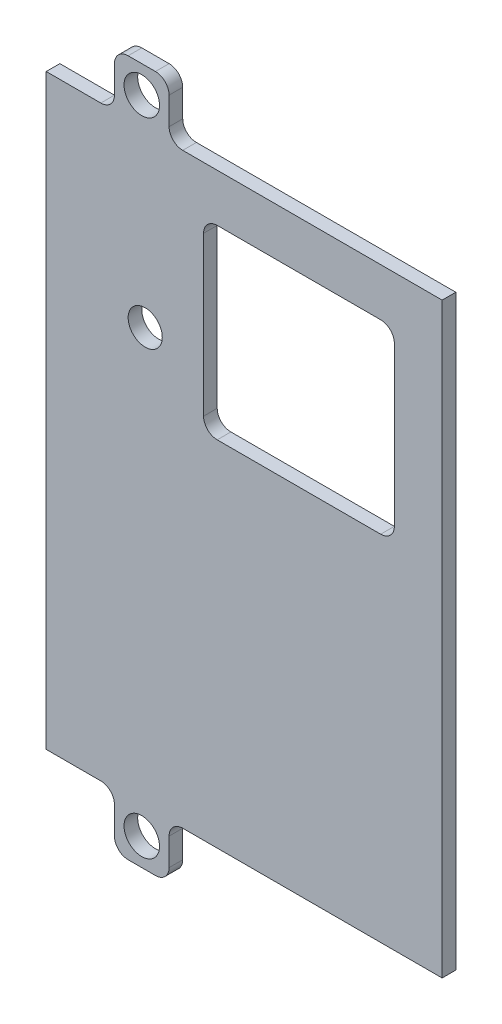
SolidWorks part; units mm, degrees
ref_plane "Front Plane" through (0, 0, 0) normal (0, 0, 1) x (1, 0, 0)
ref_plane "Top Plane" through (0, 0, 0) normal (0, 1, 0) x (1, 0, 0)
ref_plane "Right Plane" through (0, 0, 0) normal (1, 0, 0) x (0, 0, -1)
sketch "Sketch1" plane through (0, 0, 0) normal (0, 0, 1) x (1, 0, 0)
  line L35 (19.05, 113.03) -> (19.05, 107.95)
  line L36 (11.43, 115.57) -> (16.51, 115.57)
  line L37 (8.89, 107.95) -> (8.89, 113.03)
  line L38 (19.05, 113.03) -> (19.05, 107.95)
  line L39 (11.43, 115.57) -> (16.51, 115.57)
  line L40 (8.89, 107.95) -> (8.89, 113.03)
  line L50 (6.35, -3.81) -> (-3.81, -3.81)
  line L51 (-3.81, -3.81) -> (-3.81, 105.41)
  line L52 (-3.81, 105.41) -> (6.35, 105.41)
  line L53 (19.05, -6.35) -> (19.05, -11.43)
  line L54 (16.51, -13.97) -> (11.43, -13.97)
  line L55 (8.89, -11.43) -> (8.89, -6.35)
  line L56 (19.05, -6.35) -> (19.05, -11.43)
  line L57 (16.51, -13.97) -> (11.43, -13.97)
  line L58 (8.89, -11.43) -> (8.89, -6.35)
  line L59 (21.59, 105.41) -> (69.85, 105.41)
  line L60 (69.85, 105.41) -> (69.85, -3.81)
  line L61 (69.85, -3.81) -> (21.59, -3.81)
  line L66 (60.96, 96.52) -> (60.96, 61.9754)
  line L67 (25.4635, 97.409) -> (25.4635, 59.7814) construction
  line L68 (25.4635, 96.52) -> (25.4635, 61.9754)
  line L69 (25.4635, 61.9754) -> (60.96, 61.9754)
  line L71 (25.4635, 96.52) -> (60.96, 96.52)
  circle A31 centre (13.97, 110.49) radius 3.302
  circle A32 centre (13.97, 110.49) radius 3.302
  circle A34 centre (13.97, -8.89) radius 3.302
  circle A35 centre (13.97, -8.89) radius 3.302
  arc A56 (19.05, 107.95) -> (21.59, 105.41) centre (21.59, 107.95) ccw
  arc A57 (19.05, 113.03) -> (16.51, 115.57) centre (16.51, 113.03) ccw
  arc A58 (11.43, 115.57) -> (8.89, 113.03) centre (11.43, 113.03) ccw
  arc A59 (6.35, 105.41) -> (8.89, 107.95) centre (6.35, 107.95) ccw
  arc A60 (19.05, 107.95) -> (21.59, 105.41) centre (21.59, 107.95) ccw
  arc A61 (19.05, 113.03) -> (16.51, 115.57) centre (16.51, 113.03) ccw
  arc A62 (11.43, 115.57) -> (8.89, 113.03) centre (11.43, 113.03) ccw
  arc A63 (6.35, 105.41) -> (8.89, 107.95) centre (6.35, 107.95) ccw
  circle A76 centre (14.6071, 73.3808) radius 3.175
  arc A80 (21.59, -3.81) -> (19.05, -6.35) centre (21.59, -6.35) ccw
  arc A81 (16.51, -13.97) -> (19.05, -11.43) centre (16.51, -11.43) ccw
  arc A82 (8.89, -11.43) -> (11.43, -13.97) centre (11.43, -11.43) ccw
  arc A83 (8.89, -6.35) -> (6.35, -3.81) centre (6.35, -6.35) ccw
  arc A84 (21.59, -3.81) -> (19.05, -6.35) centre (21.59, -6.35) ccw
  arc A85 (16.51, -13.97) -> (19.05, -11.43) centre (16.51, -11.43) ccw
  arc A86 (8.89, -11.43) -> (11.43, -13.97) centre (11.43, -11.43) ccw
  arc A87 (8.89, -6.35) -> (6.35, -3.81) centre (6.35, -6.35) ccw
  point P11 (33.02, 96.52)
  dimension "D9" = 6.35
  dimension "D7" = 8.89
  dimension "D1" = 0
  dimension "D2" = 0
  dimension "D3" = 0
  dimension "D4" = 0
extrude "Boss-Extrude1" add sketch "Sketch1" along normal blind 2.54 contours A87 L58 A86 L57 A85 L56 A84 L61 L60 L59 A60 L38 A61 L39 A62 L40 A63 L52 L51 L50 A76 A35 A32 L66 region at (30.9201, 45.6596, 0)
sketch "Sketch3" plane through (0, 0, 0) normal (0, 0, -1) x (-1, 0, 0)
  line L0 (-69.85, -3.81) -> (-21.59, -3.81) construction
  line L1 (-37.846, -3.81) -> (-46.99, -3.81)
  line L2 (-37.846, -3.81) -> (-37.846, 0)
  line L3 (-37.846, 0) -> (-46.99, 0)
  line L4 (-46.99, -3.81) -> (-46.99, 0)
  line L5 (-37.846, -3.81) -> (-37.846, 0) construction
extrude "Boss-Extrude2" add sketch "Sketch3" along normal blind 8.89
fillet "Fillet1" radius 2.54 4 edges at (60.96, 61.9754, 1.27) (60.96, 96.52, 1.27) (25.4635, 96.52, 1.27) (25.4635, 61.9754, 1.27)
